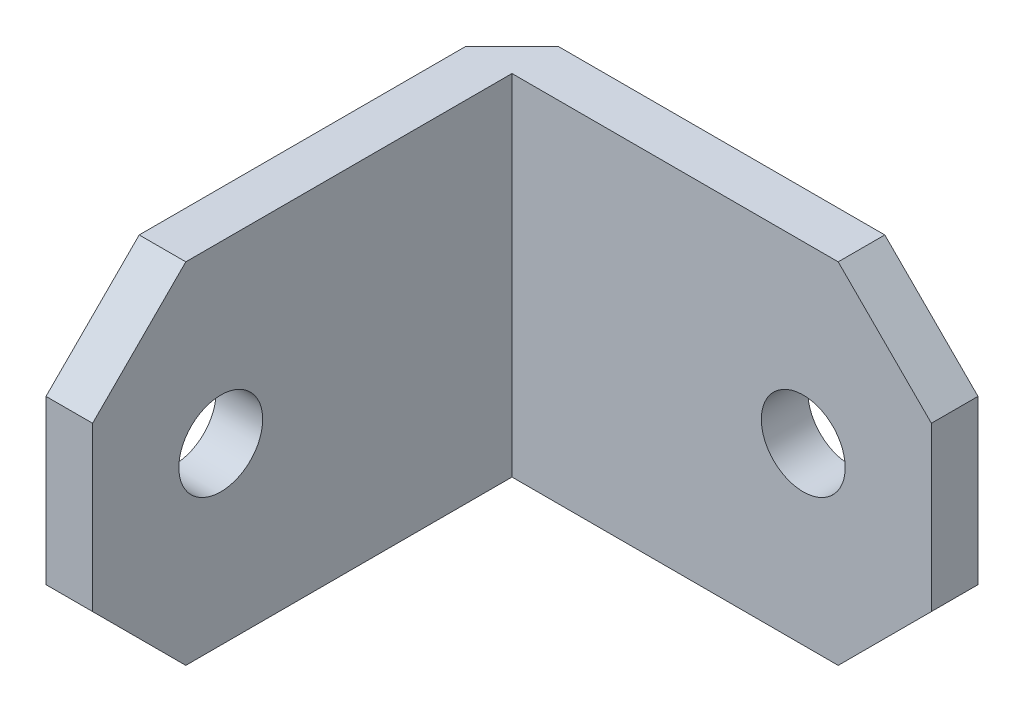
SolidWorks part; units mm, degrees
ref_plane "Front Plane" through (0, 0, 0) normal (0, 0, 1) x (1, 0, 0)
ref_plane "Top Plane" through (0, 0, 0) normal (0, 1, 0) x (1, 0, 0)
ref_plane "Right Plane" through (0, 0, 0) normal (1, 0, 0) x (0, 0, -1)
sketch "Sketch1" plane through (0, 0, 0) normal (0, 1, 0) x (1, 0, 0)
  line L1 (0, 0) -> (2.54, 0)
  line L2 (0, 0) -> (0, 25.4)
  line L4 (2.54, 0) -> (2.54, 22.86)
  line L5 (0, 25.4) -> (25.4, 25.4)
  line L6 (0, 25.4) -> (0, 14.8757)
  line L7 (2.54, 22.86) -> (25.4, 22.86)
  line L8 (25.4, 25.4) -> (25.4, 22.86)
  point P9 (0, 0)
  point P10 (-5.6769, 25.4)
  dimension "D1" = 25.4
  dimension "D2" = 25.4
  dimension "D3" = 2.54
  dimension "D4" = 2.54
extrude "Boss-Extrude1" add sketch "Sketch1" along normal blind 19.05 contours L8 L5 L2 L1 L4 L7 region at (0.3592, 0, -7.4378)
sketch "Sketch2" plane through (0, 0, -22.86) normal (0, 0, 1) x (1, 0, 0)
  line L0 (2.54, 19.05) -> (2.54, 0) construction
  line L2 (25.4, 19.05) -> (25.4, 0) construction
  circle A0 centre (18.415, 9.525) radius 2.286
  point P4 (0, 0)
  point P7 (25.4, 9.525)
  dimension "D1" = 4.572
  dimension "D2" = 15.875
extrude "Cut-Extrude1" cut sketch "Sketch2" against normal blind 2.54
sketch "Sketch3" plane through (2.54, 0, 0) normal (1, 0, 0) x (0, 0, -1)
  line L1 (22.86, 19.05) -> (22.86, 0) construction
  line L2 (0, 19.05) -> (0, 0) construction
  circle A0 centre (6.985, 9.525) radius 2.286
  point P2 (0, 0)
  point P7 (0, 9.525)
  dimension "D1" = 4.572
  dimension "D3" = 15.875
extrude "Cut-Extrude2" cut sketch "Sketch3" against normal blind 2.54
chamfer "Chamfer1" distance 5.08 angle 45 4 edges at (1.27, 0, 0) (25.4, 0, -24.13) (25.4, 19.05, -24.13) (1.27, 19.05, 0)
chamfer "Chamfer2" distance 2.54 angle 45 1 edges at (0, 9.525, -25.4)
